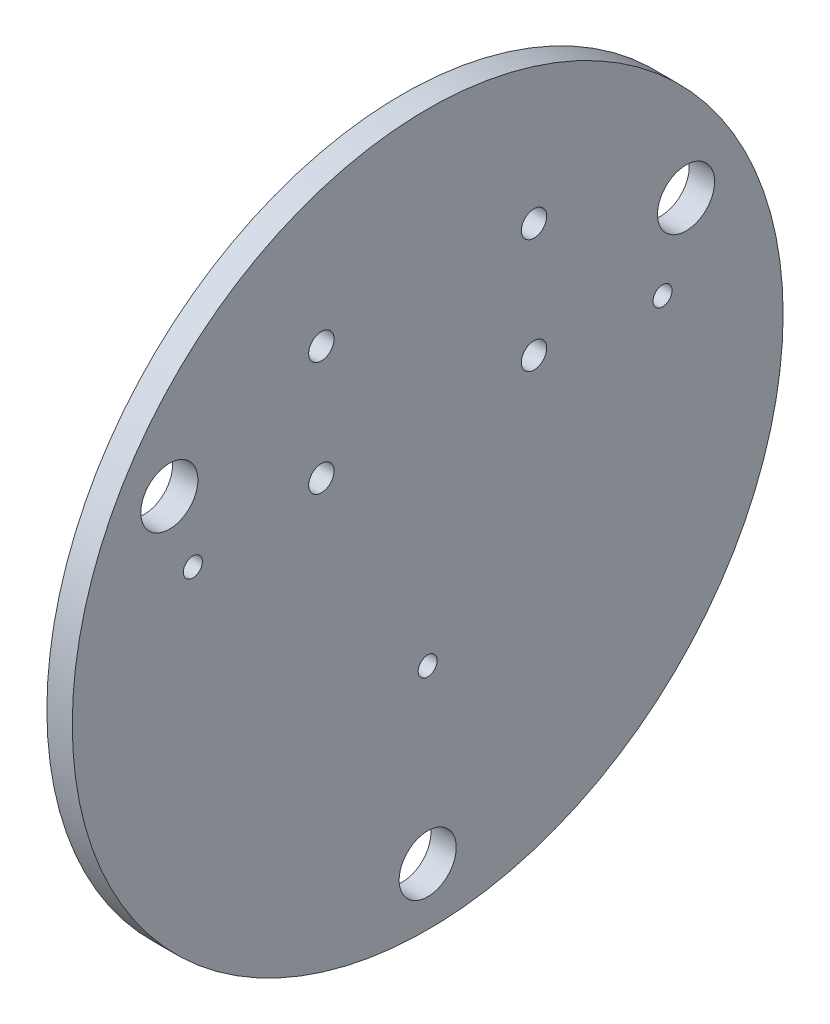
SolidWorks part; units mm, degrees
ref_plane "Ebene vorne" through (0, 0, 0) normal (0, 0, 1) x (1, 0, 0)
ref_plane "Ebene oben" through (0, 0, 0) normal (0, 1, 0) x (1, 0, 0)
ref_plane "Ebene rechts" through (0, 0, 0) normal (1, 0, 0) x (0, 0, -1)
sketch "Sketch1" plane through (0, 0, 0) normal (1, 0, 0) x (0, 0, -1)
  circle A0 centre (0, 0) radius 56
  dimension "D1" = 112
extrude "Boss-Extrude1" add sketch "Sketch1" along normal blind 4
sketch "Sketch2" plane through (0, 0, 0) normal (-1, 0, 0) x (0, 0, 1)
  line L0 (0, 0) -> (0, -56) construction
  circle A0 centre (-40.7032, 23.5) radius 4.5
  circle A1 centre (40.7032, 23.5) radius 4.5
  circle A2 centre (0, -47) radius 4.5
  circle A3 centre (0, 0) radius 56 construction
  point P9 (0, 0)
  dimension "D1" = 9
  dimension "D2" = 47
  dimension "D3" = 3
extrude "Cut-Extrude1" cut sketch "Sketch2" against normal through all
sketch "Sketch4" plane through (4, 0, 0) normal (1, 0, 0) x (0, 0, -1)
  line L0 (0, 56) -> (0, -40.0081) construction
  line L1 (16.75, 31.9955) -> (-48.2229, 31.9955) construction
  circle A0 centre (-16.75, 31.9955) radius 2
  circle A1 centre (16.75, 31.9955) radius 2
  circle A2 centre (16.75, 14) radius 2
  circle A3 centre (-16.75, 14) radius 2
  circle A4 centre (-37, 12) radius 1.5
  circle A5 centre (0, -20) radius 1.5
  circle A6 centre (37, 12) radius 1.5
  circle A7 centre (0, 0) radius 56 construction
  circle A8 centre (0, -47) radius 4.5 construction
  dimension "D1" = 4
  dimension "D2" = 3
  dimension "D5" = 33.5
  dimension "D7" = 2
  dimension "D3" = 32
  dimension "D4" = 17.9955
  dimension "D6" = 32
  dimension "D8" = 27
extrude "Cut-Extrude3" cut sketch "Sketch4" against normal through all
